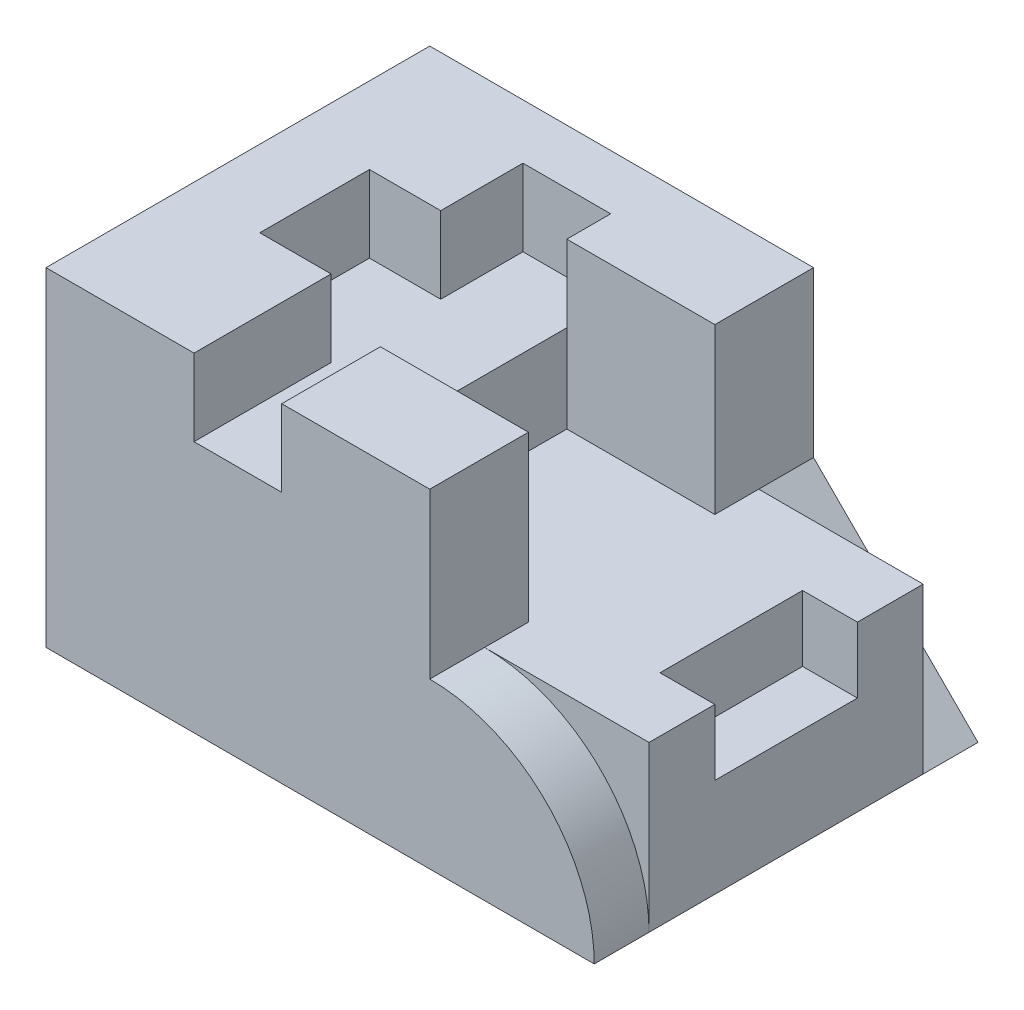
SolidWorks part; units mm, degrees
ref_plane "Спереди" through (0, 0, 0) normal (0, 0, 1) x (1, 0, 0)
ref_plane "Сверху" through (0, 0, 0) normal (0, 1, 0) x (1, 0, 0)
ref_plane "Справа" through (0, 0, 0) normal (1, 0, 0) x (0, 0, -1)
sketch "Эскиз1" plane through (0, 0, 0) normal (0, 0, 1) x (1, 0, 0)
  line L1 (-25, -15) -> (25, -15)
  line L2 (-25, -15) -> (-25, 15)
  line L3 (-25, 15) -> (25, 15)
  line L4 (25, -15) -> (25, 15)
  line L5 (-25, -15) -> (25, 15) construction
  line L6 (-25, 15) -> (25, -15) construction
  point P0 (0, 0)
  dimension "D1" = 30
  dimension "D2" = 50
extrude "Бобышка-Вытянуть1" add sketch "Эскиз1" along normal blind 35
sketch "Эскиз2" plane through (0, 0, 35) normal (0, 0, 1) x (1, 0, 0)
  line L1 (25, 15) -> (10, 15)
  line L2 (25, 15) -> (25, 0)
  line L3 (25, 0) -> (10, 0)
  line L4 (10, 15) -> (10, 0)
  dimension "D1" = 15
  dimension "D2" = 15
extrude "Вырез-Вытянуть1" cut sketch "Эскиз2" against normal through all
sketch "Эскиз3" plane through (0, 15, 0) normal (0, 1, 0) x (1, 0, 0)
  line L0 (-25, -17.5) -> (10, -17.5) construction
  line L1 (-25, -35) -> (-25, 0) construction
  line L2 (10, 0) -> (10, -35) construction
  line L3 (10, 0) -> (10, -35) construction
  line L4 (10, -22.5) -> (-18, -22.5)
  line L5 (10, -22.5) -> (10, -12.5)
  line L6 (10, -12.5) -> (-18, -12.5)
  line L7 (-18, -22.5) -> (-18, -12.5)
  line L8 (10, -22.5) -> (-18, -12.5) construction
  line L9 (10, -12.5) -> (-18, -22.5) construction
  line L10 (-7.5, -35) -> (-7.5, 0) construction
  line L11 (10, -35) -> (-25, -35) construction
  line L12 (10, 0) -> (-25, 0) construction
  line L14 (-3.5, -35) -> (-11.5, -35)
  line L15 (-3.5, -35) -> (-3.5, -5)
  line L16 (-3.5, -5) -> (-11.5, -5)
  line L17 (-11.5, -35) -> (-11.5, -5)
  line L18 (-3.5, -35) -> (-11.5, -5) construction
  line L19 (-3.5, -5) -> (-11.5, -35) construction
  point P6 (-4, -17.5)
  point P19 (-7.5, -20)
  line M1 (-25, -35) -> (10, -35)
  line M2 (10, -35) -> (10, 0)
  dimension "D1" = 7
  dimension "D2" = 10
  dimension "D3" = 30
  dimension "D4" = 8
extrude "Вырез-Вытянуть2" cut sketch "Эскиз3" against normal up to surface (15 mm away) contours L15 L4 L6 M2 region at (3.25, 15, 17.5) up to face at (17.5, 0, 17.5)
extrude "Вырез-Вытянуть3" cut sketch "Эскиз3<3>" against normal blind 7 contours L17 L15 L4 M1 | L17 L4 L15 L6 | L17 L6 L15 L16 | L4 L17 L6 L7 region at (-7.5, 15, 28.75) region at (-7.5, 15, 17.5) region at (-14.75, 15, 17.5) region at (-7.5, 15, 8.75)
sketch "Эскиз3<3>" plane through (0, 15, 0) normal (0, 1, 0) x (1, 0, 0) same geometry as "Эскиз3"
ref_plane "Плоскость1" through (0, 0, 28.75) normal (0, 0, 1) x (1, 0, 0)
ref_plane "Плоскость2" through (0, 0, 6.25) normal (0, 0, 1) x (1, 0, 0)
sketch "Эскиз6" plane through (0, 0, 0) normal (0, 1, 0) x (1, 0, 0)
  line L0 (25, -17.5) -> (-3.5, -17.5) construction
  line L1 (25, 0) -> (25, -35) construction
  line L2 (-3.5, -22.5) -> (-3.5, -12.5) construction
  line L4 (25, -24) -> (20, -24)
  line L5 (25, -24) -> (25, -11)
  line L6 (25, -11) -> (20, -11)
  line L7 (20, -24) -> (20, -11)
  line L8 (25, -24) -> (20, -11) construction
  line L9 (25, -11) -> (20, -24) construction
  point P6 (22.5, -17.5)
  dimension "D1" = 13
  dimension "D2" = 5
extrude "Вырез-Вытянуть4" cut sketch "Эскиз6" against normal blind 6
sketch "Эскиз7" plane through (0, 15, 0) normal (0, 1, 0) x (1, 0, 0)
  line L0 (-25, -17.5) -> (25, -17.5) construction
  line L1 (-25, -35) -> (-25, 0) construction
  line L2 (25, -24) -> (25, -11) construction
  line L3 (-3.5, -12.5) -> (-3.5, -5) construction
  line L4 (10, -26) -> (-3.5, -26)
  line L5 (10, -26) -> (10, -9)
  line L6 (10, -9) -> (-3.5, -9)
  line L7 (-3.5, -26) -> (-3.5, -9)
  line L8 (10, -26) -> (-3.5, -9) construction
  line L9 (10, -9) -> (-3.5, -26) construction
  line L10 (10, 0) -> (10, -12.5) construction
  point P6 (3.25, -17.5)
  dimension "D1" = 17
extrude "Вырез-Вытянуть5" cut sketch "Эскиз7" against normal up to surface (15 mm away) up to face at (14.4167, 0, 17.5)
sketch "Эскиз8" plane through (0, 0, 35) normal (0, 0, 1) x (1, 0, 0)
  line L0 (10, 0) -> (10, -15) construction
  line L1 (-25, -15) -> (25, -15) construction
  line L2 (10, 0) -> (25, 0)
  line L3 (25, 0) -> (25, -15)
  circle A0 centre (10, -15) radius 15
  line M5 (25, -15) -> (25, 0)
  line M6 (25, 0) -> (10, 0)
extrude "Вырез-Вытянуть6" cut sketch "Эскиз8" against normal blind 5 contours A0 M5 M6 region at (21.6495, -3.3505, 35)
sketch "Эскиз9" plane through (0, 0, 0) normal (0, 0, -1) x (-1, 0, 0)
  line L0 (-25, -15) -> (-10, 0)
  line L1 (-10, 0) -> (-25, 0)
  line L2 (-25, 0) -> (-25, -15)
extrude "Вырез-Вытянуть7" cut sketch "Эскиз9" against normal blind 5
